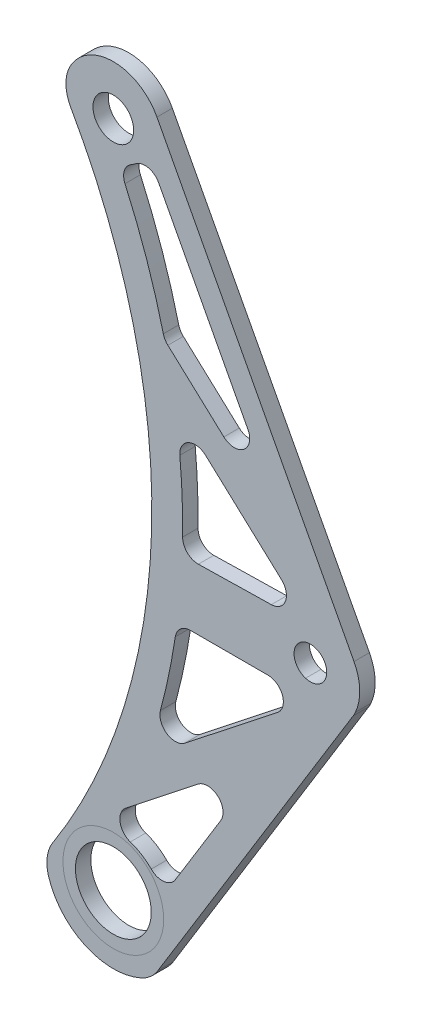
SolidWorks part; units mm, degrees
material "6061-T6 (SS)"
ref_plane "X-Y Datum" through (0, 0, 0) normal (0, 0, 1) x (1, 0, 0)
ref_plane "X-Z Datum" through (0, 0, 0) normal (0, 1, 0) x (1, 0, 0)
ref_plane "Y-Z Datum" through (0, 0, 0) normal (1, 0, 0) x (0, 0, -1)
sketch "Sketch1" plane through (0, 0, 0) normal (0, 0, 1) x (1, 0, 0)
  line L0 (0, 0) -> (0, 137.668) construction
  line L1 (0, 137.668) -> (40.5829, 60.8625) construction
  line L2 (40.5829, 60.8625) -> (0, 0) construction
  line L3 (-13.97, 0) -> (-10.16, 137.668)
  line L4 (8.9831, 142.4145) -> (49.566, 65.6091)
  line L5 (49.566, 56.116) -> (8.1778, -11.3263)
  circle A0 centre (0, 0) radius 7.8105
  circle A1 centre (40.5829, 60.8625) radius 3.3655
  circle A2 centre (0, 137.668) radius 4.191
  arc A3 (-10.16, 137.668) -> (8.9831, 142.4145) centre (0, 137.668) cw
  arc A4 (49.566, 65.6091) -> (49.566, 56.116) centre (40.5829, 60.8625) cw
  arc A5 (8.1778, -11.3263) -> (-13.97, 0) centre (0, 0) cw
  arc A6 (-10.16, 137.668) -> (-13.97, 0) centre (-120.8325, 71.8442) cw
  circle A7 centre (0, 0) radius 11.5718
  point P16 (50.7429, 60.8625)
  dimension "D4" = 15.621
  dimension "D5" = 6.731
  dimension "D6" = 8.382
  dimension "D7" = 13.97
  dimension "D8" = 10.16
  dimension "D9" = 10.16
  dimension "D1" = 137.668
  dimension "D2" = 86.868
  dimension "D3" = 73.152
  dimension "D11" = 125.83
extrude "Boss-Extrude1" add sketch "Sketch1" along normal blind 3.175 contours A3 A6 A5 L5 A4 L4 A2 A1 A0 | A6 A7 A0 region at (18.3815, 67.9714, 0) region at (-11.2445, 0, 0)
sketch "Sketch2" plane through (0, 0, 3.175) normal (0, 0, 1) x (1, 0, 0)
  line L0 (10.1927, 4.0975) -> (41.0238, 54.3369)
  line L1 (49.566, 56.116) -> (8.1778, -11.3263) construction
  line L2 (43.1498, 66.8783) -> (6.9835, 135.3251)
  line L3 (8.9831, 142.4145) -> (49.566, 65.6091) construction
  line L4 (40.4525, 67.4017) -> (14.1941, 66.8783)
  line L5 (40.5829, 54.322) -> (13.1445, 54.322)
  line L6 (40.4525, 67.4017) -> (12.627, 92.9493)
  line L7 (36.3073, 79.8281) -> (10.525, 103.4997)
  line L8 (41.0238, 54.3369) -> (6.7488, 27.3484)
  line L9 (31.426, 38.6972) -> (1.9834, 15.5138)
  arc A4 (0.9553, 130.3642) -> (-0.1973, 10.9837) centre (-120.8325, 71.8442) cw
  arc A5 (-13.97, 0) -> (-10.16, 137.668) centre (-120.8325, 71.8442) ccw construction
  circle A7 centre (0, 0) radius 10.9855
  circle A9 centre (40.5829, 60.8625) radius 6.5405
  circle A10 centre (0, 137.668) radius 7.366
  circle A11 centre (0, 137.668) radius 4.191 construction
  circle A12 centre (40.5829, 60.8625) radius 3.3655 construction
  circle A13 centre (0, 0) radius 7.8105 construction
  dimension "D3" = 3.175
  dimension "D1" = 3.175
  dimension "D2" = 3.175
  dimension "D6" = 6.35
  dimension "D4" = 5.08
  dimension "D5" = 6.35
  dimension "D7" = 6.35
  dimension "D8" = 6.35
extrude "Cut-Extrude1" cut sketch "Sketch2" against normal blind 6.35 contours A7 L0 L9 A4 | A9 L5 A4 L8 | L6 A4 L4 | A10 A4 L7 L2 region at (13.8981, 19.0703, 3.175) region at (20.6658, 45.4967, 3.175) region at (22.7156, 75.604, 3.175) region at (15.77, 109.4268, 3.175)
fillet "Fillet1" radius 3.175 14 edges at (1.9834, 15.5138, 1.5875) (-0.1973, 10.9837, 1.5875) (10.1927, 4.0975, 1.5875) (31.426, 38.6972, 1.5875) (41.0238, 54.3369, 1.5875) (6.7488, 27.3484, 1.5875) (13.1445, 54.322, 1.5875) (12.627, 92.9493, 1.5875) (14.1941, 66.8783, 1.5875) (40.4525, 67.4017, 1.5875) (36.3073, 79.8281, 1.5875) (10.525, 103.4997, 1.5875) (0.9553, 130.3642, 1.5875) (6.9835, 135.3251, 1.5875)
sketch "Sketch3" [suppressed] plane through (0, 0, 4.7625) normal (0, 0, 1) x (1, 0, 0)
  line L1 (13.9694, 0.1347) -> (39.7508, 21.6818)
  line L2 (9.979, 66.6708) -> (39.902, 40.8139)
  line L3 (55.423, 60.7241) -> (9.3949, 172.5239) construction
  line L6 (12.9992, 5.1168) -> (35.8725, 24.2335)
  line L8 (8.1778, -11.3263) -> (55.423, 52.9883) construction
  arc A0 (39.902, 40.8139) -> (35.8725, 24.2335) centre (43.2483, 31.2208) ccw
  arc A1 (-1.655, 13.8716) -> (12.9992, 5.1168) centre (0, 0) cw
  arc A3 (0.9228, 58.462) -> (-1.655, 13.8716) centre (-31.1833, 37.9483) cw
  circle A4 centre (43.2483, 31.2208) radius 10.16
  circle A5 centre (0, 0) radius 13.97
  arc A6 (0.9228, 58.462) -> (9.979, 66.6708) centre (0, 68.58) ccw
  circle A7 centre (0, 68.58) radius 10.16
  arc A8 (-5.9452, 60.3411) -> (-7.4548, 11.8147) centre (-23.0858, 36.5876) cw
  arc A9 (-13.4408, 9.525) -> (-10.5128, 62.23) centre (-35.7711, 37.1994) ccw construction
  dimension "D1" = 10.16
  dimension "D2" = 10.16
  dimension "D3" = 13.97
  dimension "D6" = 6.7275
  dimension "D9" = 12.7
  dimension "D7" = 38.1
  dimension "D4" = 29.81
  dimension "D5" = 5.08
  dimension "D8" = 5.08
  dimension "D11" = 75.318
extrude "Cut-Extrude2" [suppressed] cut sketch "Sketch3" against normal blind 6.35 contours A6 A3 A1 L6 A0 L2 | A5 L1 A4 L6 | L6 A0 L2 A6 A3 A1
sketch3d "3DSketch1" [suppressed]
  line L0 (0, 137.668, 3.175) -> (0, 137.668, 0) construction
  line L1 (40.5829, 60.8625, 3.175) -> (40.5829, 60.8625, 0) construction
  point P0 (0, 137.668, 3.175)
  point P1 (40.5829, 60.8625, 3.175)
fillet "Fillet2" [suppressed] radius 6.35
fillet "Fillet4" [suppressed] radius 6.35
ref_axis "Axis1" through (0, 137.668, 3.175) along (0, 0, -1)
ref_axis "Axis2" through (40.5829, 60.8625, 3.175) along (0, 0, -1)
ref_plane "Plane1" through (23.5426, 4.1512, 0) normal (0.9848, 0.1736, 0) x (0, 0, -1)
ref_plane "Plane2" through (19.8415, -6.142, 0) normal (0.9553, -0.2957, 0) x (0, 0, -1)
sketch "Sketch4" [suppressed] plane through (23.5426, 4.1512, 0) normal (0.9848, 0.1736, 0) x (0, 0, -1)
  line L0 (-3.175, 166.0937) -> (-3.175, 170.2847)
sketch "Sketch5" [suppressed] plane through (19.8415, -6.142, 0) normal (0.9553, -0.2957, 0) x (0, 0, -1)
  line L0 (-3.175, 70.1413) -> (-3.175, 11.4039)
  line L1 (-0.3461, 48.6622) -> (-0.3461, 36.6839)
split line "Split Line1"
split line "Split Line2" [suppressed]
ref_point "Point2"
ref_axis "Axis3" through (0, 0, 3.175) along (0, 0, -1)
sketch "Sketch6" plane through (0, 0, 3.175) normal (0, 0, -1) x (-1, 0, 0)
  circle A0 centre (0, 0) radius 10.3708
split line "Split Line3"
fillet "Fillet5" radius 7.62 4 edges at (-13.97, 0, 1.5875) (-10.16, 137.668, 1.5875) (49.566, 56.116, 1.5875) (8.1778, -11.3263, 1.5875)
ref_point "Point4"
